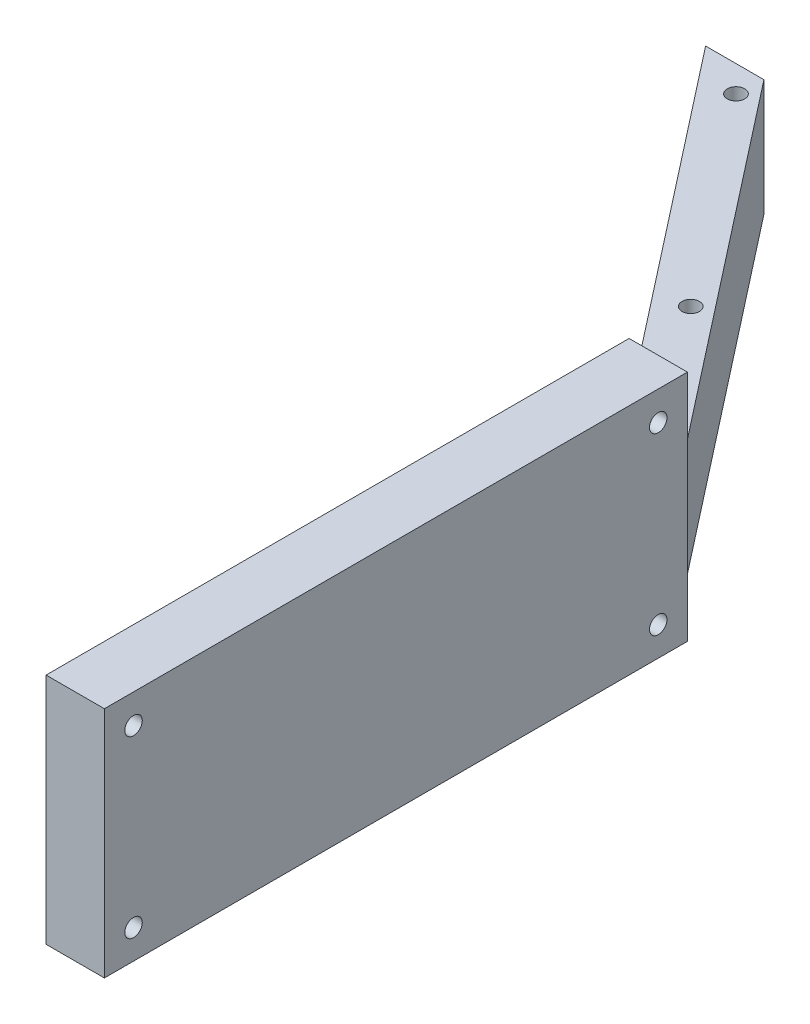
SolidWorks part; units mm, degrees
ref_plane "前视基准面" through (0, 0, 0) normal (0, 0, 1) x (1, 0, 0)
ref_plane "上视基准面" through (0, 0, 0) normal (0, 1, 0) x (1, 0, 0)
ref_plane "右视基准面" through (0, 0, 0) normal (1, 0, 0) x (0, 0, -1)
other "Configuration Table"
sketch "草图1" plane through (0, 0, 0) normal (1, 0, 0) x (0, 0, -1)
  line L1 (-50, 20) -> (50, 20)
  line L2 (-50, 20) -> (-50, -20)
  line L3 (-50, -20) -> (50, -20)
  line L4 (50, 20) -> (50, -20)
  dimension "D1" = 100
  dimension "D2" = 40
  dimension "D3" = 20
  dimension "D4" = 50
extrude "凸台-拉伸1" add sketch "草图1" along normal blind 10
sketch "草图3" plane through (0, 20, 0) normal (0, 1, 0) x (1, 0, 0)
  line L0 (10, 50) -> (-36.8771, 110)
  line L4 (-46.8771, 110) -> (0, 50)
  line L5 (10, 50) -> (0, 50) construction
  line L6 (0, 50) -> (10, 50)
  line L7 (-46.8771, 110) -> (-36.8771, 110)
  dimension "D1" = 10
  dimension "D2" = 52
  dimension "D5" = 60
extrude "凸台-拉伸2" add sketch "草图3" against normal blind 30
sketch "草图4" plane through (0, 20, 0) normal (0, 1, 0) x (1, 0, 0)
  line L0 (-37.1684, 105.5) -> (-9.4636, 70.0395) construction
  line L1 (10, 50) -> (-36.8771, 110) construction
  line L2 (-36.8771, 110) -> (-46.8771, 110) construction
  circle A0 centre (-37.1684, 105.5) radius 1.5
  circle A1 centre (-9.4636, 70.0395) radius 1.5
  dimension "D1" = 45
  dimension "D2" = 3
  dimension "D3" = 3
  dimension "D4" = 3
  dimension "D5" = 4.5
extrude "切除-拉伸1" cut sketch "草图4" against normal through all
sketch "草图5" plane through (0, 20, 0) normal (0, 1, 0) x (1, 0, 0)
  line L0 (10, 50) -> (0, 50)
  line L1 (0, 50) -> (-46.8771, 110)
  line L2 (-46.8771, 110) -> (-36.8771, 110)
  line L3 (-36.8771, 110) -> (10, 50)
extrude "切除-拉伸2" cut sketch "草图5" against normal blind 10
sketch "草图7" plane through (10, 0, 0) normal (1, 0, 0) x (0, 0, -1)
  line L0 (50, 20) -> (-50, 20) construction
  line L1 (-45, 15) -> (45, 15) construction
  line L2 (-45, 15) -> (-45, -15) construction
  line L3 (-45, -15) -> (45, -15) construction
  line L4 (45, 15) -> (45, -15) construction
  line L5 (50, -10) -> (50, 10) construction
  circle A0 centre (-45, 15) radius 1.5
  circle A1 centre (-45, -15) radius 1.5
  circle A2 centre (45, -15) radius 1.5
  circle A3 centre (45, 15) radius 1.5
  dimension "D3" = 3
  dimension "D4" = 3
  dimension "D5" = 3
  dimension "D6" = 3
  dimension "D1" = 90
  dimension "D2" = 30
  dimension "D7" = 5
  dimension "D8" = 5
extrude "切除-拉伸3" cut sketch "草图7" against normal blind 10
chamfer "倒角2" distance 0.5 angle 45 4 edges at (0, 15, -46.5) (0, -15, -46.5) (0, -15, 43.5) (0, 15, 43.5)
sketch "草图9" plane through (0, 0, 0) normal (0, 1, 0) x (1, 0, 0)
  line L0 (-9.2349, 61.8202) -> (-12.3397, 59.3944)
  line L1 (-46.8771, 110) -> (0, 50) construction
  line L2 (-12.3397, 59.3944) -> (-5, 50)
  line L3 (-5, 50) -> (-5, 20)
  line L4 (-5, 20) -> (0, 20)
  line L5 (0, 50) -> (0, -50) construction
  line L6 (-9.2349, 61.8202) -> (0, 50)
  line L7 (0, 50) -> (0, 20)
  point P4 (0, 0)
  dimension "D1" = 30
  dimension "D2" = 15
  dimension "D4" = 5
extrude "凸台-拉伸3" add sketch "草图9" along normal blind 6 and the other way blind 6
fillet "圆角1" radius 5 2 edges at (-5, 0, -20) (-12.3397, 0, -59.3944)
